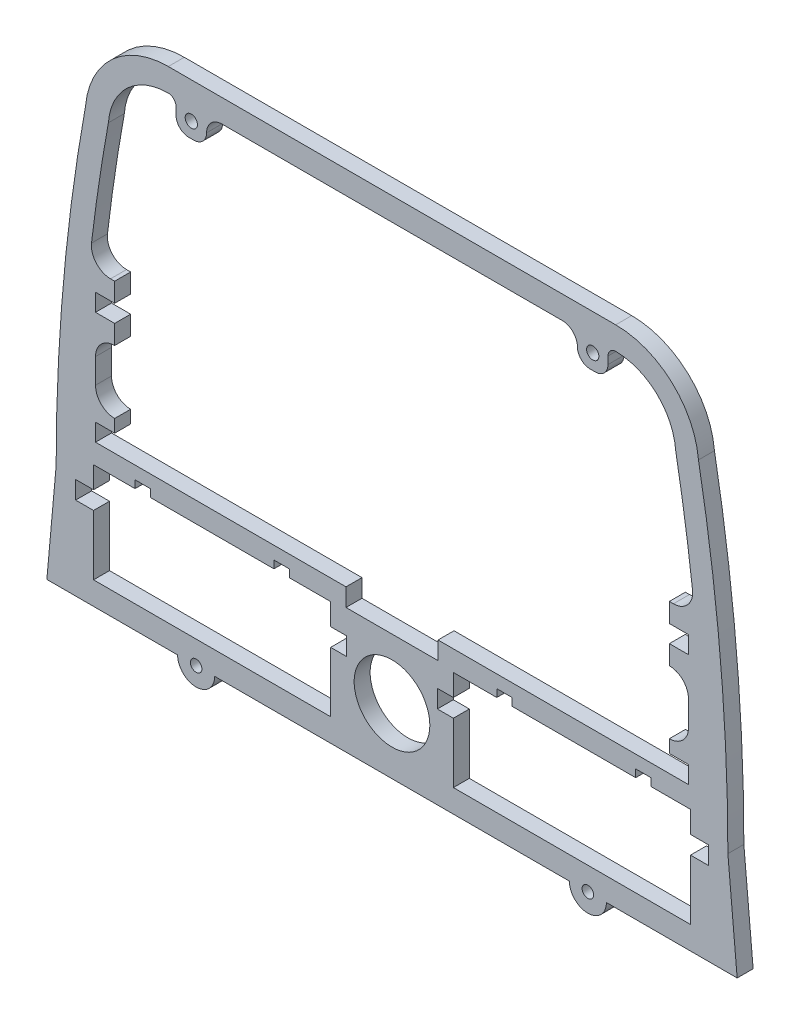
SolidWorks part; units mm, degrees
material "Delrin 2700 NC010, Low Viscosity Acetal Copolymer (SS)"
ref_plane "Front Plane" through (0, 0, 0) normal (0, 0, 1) x (1, 0, 0)
ref_plane "Top Plane" through (0, 0, 0) normal (0, 1, 0) x (1, 0, 0)
ref_plane "Right Plane" through (0, 0, 0) normal (1, 0, 0) x (0, 0, -1)
sketch "Sketch1" plane through (0, 0, 0) normal (0, 0, 1) x (1, 0, 0)
  line L0 (33.3676, -11.9888) -> (34.29, -22.225)
  line L1 (22.225, 27.94) -> (-22.225, 27.94)
  line L2 (-34.29, -22.225) -> (-30.4467, 20.4259) construction
  line L3 (-33.3676, -11.9888) -> (-33.3676, 14.6458) construction
  line L4 (-33.3676, -11.9888) -> (-34.29, -22.225)
  line L5 (16.9079, 25.654) -> (-16.9079, 25.654)
  line L6 (6.096, -13.97) -> (6.096, -19.939)
  line L7 (-29.6529, -19.939) -> (-6.096, -19.939)
  line L8 (-34.29, -22.225) -> (-21.299, -22.225)
  line L9 (-29.6529, -10.033) -> (-29.6529, -12.192)
  line L10 (18.4213, 24.1407) -> (18.4213, 24.1363)
  line L11 (19.6913, 22.8663) -> (20.1867, 22.8663)
  line L12 (21.4567, 24.1363) -> (21.4567, 24.8713)
  line L13 (-21.4567, 24.1363) -> (-21.4567, 24.8713)
  line L14 (-19.6913, 22.8663) -> (-20.1867, 22.8663)
  line L15 (-18.4213, 24.1407) -> (-18.4213, 24.1363)
  line L16 (29.4572, -8.001) -> (4.572, -8.001)
  line L17 (29.6529, -10.033) -> (25.7309, -10.033)
  line L18 (0, 18.415) -> (0, -18.415) construction
  line L19 (-1007.9925, 0) -> (48992.0075, 0) construction
  line L20 (-6.096, -10.033) -> (-10.2069, -10.033)
  line L21 (19.939, 24.384) -> (21.4567, 24.384) construction
  line L22 (6.096, -19.939) -> (29.6529, -19.939)
  line L23 (-6.096, -10.033) -> (-6.096, -12.192)
  line L24 (5.9491, -2.2098) -> (59.5431, -2.2098) construction
  line L25 (5.9491, -2.2098) -> (5.9491, -11.9888) construction
  line L26 (3.4091, -11.9888) -> (-3.4091, -11.9888) construction
  line L27 (59.5431, -2.2098) -> (59.5431, -11.9888) construction
  line L28 (-31.7887, -19.939) -> (31.7887, -19.939) construction
  line L29 (22.225, 25.654) -> (-22.225, 25.654) construction
  line L30 (-6.096, -19.939) -> (-6.1666, -19.9899)
  line L31 (29.4572, -6.2738) -> (27.5522, -6.2738)
  line L32 (27.5522, -6.2738) -> (27.5522, -5.0038)
  line L33 (-29.6529, -12.192) -> (-31.4309, -12.192)
  line L34 (27.5522, -5.0038) -> (29.4572, -5.0038)
  line L35 (29.4572, 1.27) -> (27.5522, 1.27)
  line L36 (27.5522, 1.27) -> (27.5522, 3.175)
  line L37 (27.5522, 3.175) -> (29.4572, 3.175)
  line L38 (29.4572, 4.9022) -> (27.5522, 4.9022)
  line L39 (19.939, 24.384) -> (18.4213, 24.384) construction
  line L40 (27.5522, 4.9022) -> (27.5522, 6.8072)
  line L41 (27.5522, 6.8072) -> (30.0922, 6.8072)
  line L42 (19.939, 24.384) -> (19.939, 22.8663) construction
  line L43 (6.096, -10.033) -> (6.096, -12.192)
  line L44 (-29.4572, -6.2738) -> (-29.4572, -8.001)
  line L45 (-29.4572, -6.2738) -> (-27.5522, -6.2738)
  line L46 (-27.5522, -6.2738) -> (-27.5522, -5.0038)
  line L47 (-27.5522, -5.0038) -> (-29.4572, -5.0038)
  line L48 (-29.4572, 1.27) -> (-29.4572, -5.0038)
  line L49 (-29.4572, 1.27) -> (-27.5522, 1.27)
  line L50 (-27.5522, 1.27) -> (-27.5522, 3.175)
  line L51 (-27.5522, 3.175) -> (-29.4572, 3.175)
  line L52 (-29.4572, 4.9022) -> (-29.4572, 3.175)
  line L53 (-31.4309, -12.192) -> (-31.4309, -13.97)
  line L54 (-31.4309, -13.97) -> (-29.6529, -13.97)
  line L55 (-6.096, -12.192) -> (-4.5069, -12.192)
  line L56 (-4.5069, -12.192) -> (-4.5069, -13.97)
  line L57 (-4.5069, -13.97) -> (-6.096, -13.97)
  line L58 (-29.6529, -10.033) -> (-29.6529, -19.939) construction
  line L59 (-29.6529, -14.986) -> (-33.4249, -14.986) construction
  line L60 (-29.6529, -14.986) -> (-0.4824, -14.986) construction
  line L61 (-6.096, -13.97) -> (-6.096, -19.939)
  line L62 (-29.6529, -19.939) -> (-29.6529, -13.97)
  line L63 (29.6529, -19.939) -> (29.6529, -13.97)
  line L64 (-31.0816, -12.0913) -> (-31.7887, -19.939) construction
  line L65 (29.6529, -10.033) -> (29.6529, -12.192)
  line L66 (31.4309, -13.97) -> (29.6529, -13.97)
  line L67 (31.4309, -12.192) -> (31.4309, -13.97)
  line L68 (29.6529, -12.192) -> (31.4309, -12.192)
  line L69 (6.096, -12.192) -> (4.5069, -12.192)
  line L70 (4.5069, -12.192) -> (4.5069, -13.97)
  line L71 (4.5069, -13.97) -> (6.096, -13.97)
  line L72 (29.4572, 4.9022) -> (29.4572, 3.175)
  line L73 (31.0816, -12.0913) -> (31.7887, -19.939) construction
  line L74 (29.4572, 1.27) -> (29.4572, -5.0038)
  line L75 (29.4572, -6.2738) -> (29.4572, -8.001)
  line L76 (-29.4572, 4.9022) -> (-27.5522, 4.9022)
  line L77 (-27.5522, 4.9022) -> (-27.5522, 6.8072)
  line L78 (-27.5522, 6.8072) -> (-30.0922, 6.8072)
  line L79 (-17.616, -22.225) -> (17.616, -22.225)
  line L80 (21.299, -22.225) -> (34.29, -22.225)
  line L81 (-34.29, -22.225) -> (34.29, -22.225) construction
  line L82 (-4.572, -8.001) -> (-4.572, -9.779)
  line L83 (-4.572, -9.779) -> (0, -9.779)
  line L84 (0, -9.779) -> (4.572, -9.779)
  line L85 (4.572, -9.779) -> (4.572, -8.001)
  line L86 (-4.572, -8.001) -> (-29.4572, -8.001)
  line L99 (0, -32.131) -> (0, -22.225) construction
  line L115 (-11.7309, -10.033) -> (-24.0069, -10.033)
  line L117 (11.9309, -10.1918) -> (10.4069, -10.1918) construction
  line L118 (-24.0069, -10.1917) -> (-25.5309, -10.1917) construction
  line L119 (-25.5309, -10.033) -> (-29.6529, -10.033)
  line L120 (10.4069, -10.033) -> (6.096, -10.033)
  line L121 (-10.2069, -10.1918) -> (-11.7309, -10.1918) construction
  line L122 (25.7309, -10.1918) -> (24.2069, -10.1918) construction
  line L123 (24.2069, -10.033) -> (11.9309, -10.033)
  line L125 (11.9309, -10.1918) -> (10.4069, -10.1918) construction
  line L126 (-24.0069, -10.1917) -> (-25.5309, -10.1917) construction
  line L136 (-10.2069, -10.1918) -> (-11.7309, -10.1918) construction
  line L137 (25.7309, -10.1918) -> (24.2069, -10.1918) construction
  line L138 (-25.5309, -10.1917) -> (-25.5309, -9.271)
  line L139 (-25.5309, -9.271) -> (-24.0069, -9.271)
  line L140 (-24.0069, -9.271) -> (-24.0069, -10.1917)
  line L141 (-11.7309, -10.1918) -> (-11.7309, -9.271)
  line L142 (-11.7309, -9.271) -> (-10.2069, -9.271)
  line L143 (-10.2069, -9.271) -> (-10.2069, -10.1918)
  line L144 (10.4069, -10.1918) -> (10.4069, -9.271)
  line L145 (10.4069, -9.271) -> (11.9309, -9.271)
  line L146 (11.9309, -9.271) -> (11.9309, -10.1918)
  line L147 (24.2069, -10.1918) -> (24.2069, -9.271)
  line L155 (24.2069, -9.271) -> (25.7309, -9.271)
  line L156 (25.7309, -9.271) -> (25.7309, -10.1918)
  arc A0 (22.225, 27.94) -> (30.4467, 20.4259) centre (22.225, 19.685) cw
  arc A1 (-22.225, 27.94) -> (-30.4467, 20.4259) centre (-22.225, 19.685) ccw
  arc A2 (33.3676, -11.9888) -> (30.4467, 20.4259) centre (-147.9525, -11.9888) ccw
  circle A3 centre (0, -15.748) radius 3.7592
  circle A4 centre (19.4575, -22.225) radius 0.5715
  arc A5 (-33.3676, -11.9888) -> (-30.4467, 20.4259) centre (147.9525, -11.9888) cw
  arc A6 (-17.616, -22.225) -> (-21.299, -22.225) centre (-19.4575, -22.225) cw
  arc A7 (17.616, -22.225) -> (21.299, -22.225) centre (19.4575, -22.225) ccw
  arc A8 (20.1867, 22.8663) -> (21.4567, 24.1363) centre (20.1867, 24.1363) ccw
  circle A9 centre (-19.939, 24.384) radius 0.6096
  circle A10 centre (19.939, 24.384) radius 0.6096
  arc A11 (18.4213, 24.1363) -> (19.6913, 22.8663) centre (19.6913, 24.1363) ccw
  circle A12 centre (-19.4575, -22.225) radius 0.5715
  arc A13 (18.4213, 24.1407) -> (16.9079, 25.654) centre (16.9079, 24.1407) ccw
  arc A14 (22.2416, 25.654) -> (21.4567, 24.8713) centre (22.2394, 24.8713) ccw
  arc A15 (-22.2416, 25.654) -> (-21.4567, 24.8713) centre (-22.2394, 24.8713) cw
  arc A16 (-20.1867, 22.8663) -> (-21.4567, 24.1363) centre (-20.1867, 24.1363) cw
  arc A17 (-18.4213, 24.1363) -> (-19.6913, 22.8663) centre (-19.6913, 24.1363) cw
  arc A18 (-22.2416, 25.654) -> (-28.1777, 20.1262) centre (-22.225, 19.685) ccw
  arc A19 (-18.4213, 24.1407) -> (-16.9079, 25.654) centre (-16.9079, 24.1407) cw
  arc A20 (31.0816, -12.0913) -> (31.0816, -11.9888) centre (-147.9525, -11.9888) ccw
  circle A21 centre (-19.4575, -22.225) radius 1.8415 construction
  arc A23 (22.2416, 25.654) -> (28.1777, 20.1262) centre (22.225, 19.685) cw
  arc A25 (-22.225, 25.654) -> (-28.1777, 20.1262) centre (-22.225, 19.685) ccw construction
  arc A26 (22.225, 25.654) -> (28.1777, 20.1262) centre (22.225, 19.685) cw construction
  arc A28 (-31.0816, -12.0913) -> (-28.1777, 20.1262) centre (147.9525, -11.9888) cw construction
  arc A30 (31.0816, -12.0913) -> (28.1777, 20.1262) centre (-147.9525, -11.9888) ccw construction
  arc A31 (30.0922, 6.8072) -> (28.1777, 20.1262) centre (-147.9525, -11.9888) ccw
  arc A33 (-30.0922, 6.8072) -> (-28.1777, 20.1262) centre (147.9525, -11.9888) cw
  point P0 (0, 0)
  point P1 (0, 27.94)
  point P31 (0, -11.9888)
  point P121 (-30.9018, -14.986)
  point P135 (-17.616, -22.225)
  point P160 (-15.7485, -22.098)
  point P161 (-15.7485, -28.448)
  point P166 (15.7485, -28.448)
  point P167 (15.7485, -22.098)
  dimension "D4" = 2.286
  dimension "D6" = 8.255
  dimension "D7" = 19.4575
  dimension "D8" = 50.165
  dimension "D9" = 15.748
  dimension "D5" = 1.2192
  dimension "D17" = 1.143
  dimension "D3" = 7.5184
  dimension "D18" = 1.27
  dimension "D19" = 1.27
  dimension "D26" = 11.176
  dimension "D28" = 0.7827
  dimension "D29" = 1.5133
  dimension "D32" = 1.778
  dimension "D2" = 44.45
  dimension "D10" = 1.27
  dimension "D11" = 1.27
  dimension "D12" = 68.58
  dimension "D13" = 19.939
  dimension "D14" = 22.225
  dimension "D15" = 53.594
  dimension "D16" = 9.779
  dimension "D20" = 6.096
  dimension "D21" = 11.938
  dimension "D22" = 2.032
  dimension "D23" = 1.7272
  dimension "D24" = 1.27
  dimension "D25" = 1.905
  dimension "D27" = 0.4954
  dimension "D30" = 1.905
  dimension "D31" = 1.7272
  dimension "D33" = 1.778
  dimension "D34" = 2.159
  dimension "D35" = 23.5569
  dimension "D36" = 26.924
  dimension "D37" = 1.905
  dimension "D38" = 2.54
  dimension "D39" = 1.778
  dimension "D40" = 9.144
  dimension "D42" = 0.762
extrude "Boss-Extrude1" add sketch "Sketch1" along normal blind 1.5875 contours L8 A12 A4 L0 A2 A0 L1 A1 A5 L4 L74 L16 A18 A15 L13 A16 L14 A17 L15 A19 L5 A13 L10 A11 L11 A8 L12 A14 A23 A20 L22 L43 L17 A10 A9 A3 L20 region at (32.9716, -17.1841, 0)
ref_axis "Axis1" through (0, -15.748, 0) along (0, 0, 1)
fillet "Fillet2" radius 1.905 6 edges at (-29.4572, 1.27, 0.7937) (-29.4572, -5.0038, 0.7937) (-30.0922, 6.8072, 0.7937) (29.4572, -5.0038, 0.7937) (29.4572, 1.27, 0.7937) (30.0922, 6.8072, 0.7937)
